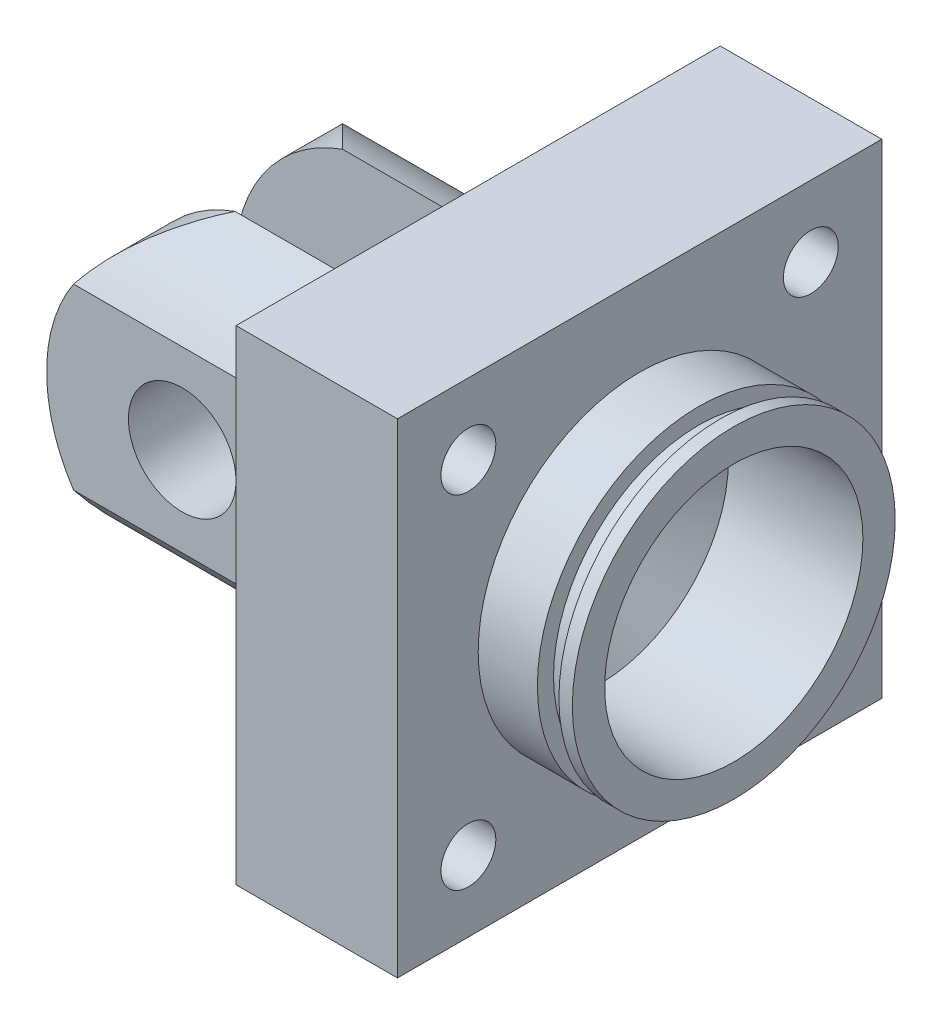
SolidWorks part; units mm, degrees
ref_plane "Front Plane" through (0, 0, 0) normal (0, 0, 1) x (1, 0, 0)
ref_plane "Top Plane" through (0, 0, 0) normal (0, 1, 0) x (1, 0, 0)
ref_plane "Right Plane" through (0, 0, 0) normal (1, 0, 0) x (0, 0, -1)
sketch "Sketch1" plane through (0, 0, 0) normal (0, 0, 1) x (1, 0, 0)
  line L0 (0, 0) -> (55.2, 0)
  dimension "D1" = 55.2
revolve "Revolve-Thin1" add sketch "Sketch1" angle 360 about L0 wall 30
sketch "Sketch2" plane through (55.2, 0, 0) normal (1, 0, 0) x (0, 0, -1)
  line L1 (-45, 45) -> (45, 45)
  line L2 (-45, 45) -> (-45, -45)
  line L3 (-45, -45) -> (45, -45)
  line L4 (45, 45) -> (45, -45)
  line L5 (-45, 45) -> (45, -45) construction
  line L6 (-45, -45) -> (45, 45) construction
  point P0 (0, 0)
  dimension "D1" = 90
  dimension "D2" = 90
extrude "Boss-Extrude1" add sketch "Sketch2" along normal blind 30
sketch "Sketch8" plane through (0, 0, 0) normal (0, 0, 1) x (1, 0, 0)
  line L0 (0, 0) -> (96.2, 0)
  dimension "D1" = 96.2
revolve "Revolve-Thin2" add sketch "Sketch8" angle 360 about L0 wall 30
sketch "Sketch11" plane through (0, 0, 0) normal (0, 1, 0) x (1, 0, 0)
  line L0 (0, 0) -> (100.2, 0)
  dimension "D1" = 100.2
revolve "Revolve-Thin3" add sketch "Sketch11" angle 360 about L0 wall 27
sketch "Sketch14" plane through (100.2, 0, 0) normal (1, 0, 0) x (0, 0, -1)
  point P0 (0, 0)
sketch "Sketch15" plane through (0, 0, 0) normal (0, 0, 1) x (1, 0, 0)
  line L0 (100.2, 0) -> (102.7, 0)
  dimension "D1" = 2.5
revolve "Revolve-Thin4" add sketch "Sketch15" angle 360 about L0 wall 30
sketch "Sketch16" plane through (0, 0, 0) normal (-1, 0, 0) x (0, 0, 1)
  line L1 (-10, -35.8221) -> (10, -35.8221)
  line L2 (-10, -35.8221) -> (-10, 35.8221)
  line L3 (-10, 35.8221) -> (10, 35.8221)
  line L4 (10, -35.8221) -> (10, 35.8221)
  line L5 (-10, -35.8221) -> (10, 35.8221) construction
  line L6 (-10, 35.8221) -> (10, -35.8221) construction
  point P0 (0, 0)
  dimension "D1" = 20
extrude "Cut-Extrude1" cut sketch "Sketch16" against normal blind 55.2
sketch "Sketch17" plane through (0, 0, 0) normal (-1, 0, 0) x (0, 0, 1)
  line L1 (-25, -36.9353) -> (25, -36.9353)
  line L2 (-25, -36.9353) -> (-25, 36.9353)
  line L3 (-25, 36.9353) -> (25, 36.9353)
  line L4 (25, -36.9353) -> (25, 36.9353)
  line L5 (-25, -36.9353) -> (25, 36.9353) construction
  line L6 (-25, 36.9353) -> (25, -36.9353) construction
  point P0 (0, 0)
  dimension "D1" = 50
extrude "Cut-Extrude2" cut sketch "Sketch17" against normal blind 55.2 flip side to cut
sketch "Sketch19" plane through (0, 0, 25) normal (0, 0, 1) x (1, 0, 0)
  circle A0 centre (25.2, 0) radius 10
  dimension "D2" = 20
  dimension "D1" = 25.2
extrude "Cut-Extrude3" cut sketch "Sketch19" against normal through all
sketch "Sketch22" plane through (0, 0, -25) normal (0, 0, -1) x (-1, 0, 0)
  line L1 (-23.6499, 34.3605) -> (9.9849, 34.3605)
  line L2 (-23.6499, 34.3605) -> (-23.6499, -35.6681)
  line L3 (-23.6499, -35.6681) -> (9.9849, -35.6681)
  line L4 (9.9849, 34.3605) -> (9.9849, -35.6681)
  line L5 (-23.6499, 34.3605) -> (9.9849, -35.6681) construction
  line L6 (-23.6499, -35.6681) -> (9.9849, 34.3605) construction
  circle A0 centre (-30, 0) radius 30
  point P3 (-6.8325, -0.6538)
  line M7 (0, -16.5831) -> (0, 16.5831)
  line M8 (0, 16.5831) -> (-55.2, 16.5831)
  line M10 (-55.2, -16.5831) -> (0, -16.5831)
  dimension "D1" = 60
extrude "Cut-Extrude4" cut sketch "Sketch22" against normal through all contours A0 M7 M8 | A0 L2 L3 L4 L1 M8 M7 M10 | A0 M10 M7 region at (6.8325, 33.5836, -25) region at (1.4758, 12.5096, -25) region at (1.4758, -12.5096, -25)
hole_wizard "Tap Drill for M1.2x0.25 Tap2" positions "Sketch25" profile "Sketch26" hole size "M1.2x0.25" standard "ISO"
sketch "Sketch25" plane through (102.7, 0, 0) normal (1, 0, 0) x (0, 0, -1)
  point P0 (0, 0)
sketch "Sketch26" plane through (102.7, 0, 0) normal (0, 1, 0) x (0, 0, -1)
  line L0 (0, 0) -> (0, 39.4207)
  line L1 (0, 39.4207) -> (24, 25)
  line L2 (24, 25) -> (24, 0)
  line L5 (24, 0) -> (0, 0)
  line L10 (0, 39.4207) -> (-24, 25) construction
  line L11 (0, -6.35) -> (0, 107.95) construction
  dimension "Hole Dia." = 48
  dimension "Hole Depth" = 25
  dimension "Drill Angle" = 118
sketch "Sketch30" plane through (85.2, 0, 0) normal (1, 0, 0) x (0, 0, -1)
  line L0 (-45, -45) -> (-31.8198, -31.8198)
  circle A0 centre (0, 0) radius 45
hole_wizard "M12 Tapped Hole2" positions "Sketch31" profile "Sketch32" tap size "M12" standard "ISO"
sketch "Sketch31" plane through (85.2, 0, 0) normal (1, 0, 0) x (0, 0, -1)
  point P0 (-31.8198, -31.8198)
sketch "Sketch32" plane through (85.2, -31.8198, 31.8198) normal (0, 1, 0) x (0, 0, -1)
  line L0 (0, 0) -> (0, 23.0644)
  line L1 (0, 23.0644) -> (5.1, 20)
  line L2 (5.1, 20) -> (5.1, 0)
  line L5 (5.1, 0) -> (0, 0)
  line L10 (0, 23.0644) -> (-5.1, 20) construction
  line L11 (0, -6.35) -> (0, 107.95) construction
  dimension "Tap Drill Dia." = 10.2
  dimension "Tap Drill Depth" = 20
  dimension "Drill Angle" = 118
cosmetic thread "Hole Thread5" parameters "D1"=15, "D2"=11.2
pattern_circular "CirPattern1" count 4 every 90 about axis through (77.7, 0, 0) along (-1, 0, 0) of "M12 Tapped Hole2" reverse direction yes
cosmetic thread "Hole Thread6" parameters "D1"=15, "D2"=11.2
cosmetic thread "Hole Thread7" parameters "D1"=15, "D2"=11.2
cosmetic thread "Hole Thread8" parameters "D1"=15, "D2"=11.2
sketch "Sketch43" plane through (0, -45, 0) normal (0, -1, 0) x (-1, 0, 0)
  point P0 (-70.2, 0)
hole_wizard "M16x1.5 Tapped Hole3" positions "3DSketch7" profile "Sketch44" tap size "M16x1.5" standard "ISO"
sketch3d "3DSketch7"
  point P0 (70.2, -45, 0)
sketch "Sketch44" plane through (70.2, -45, 0) normal (1, 0, 0) x (0, 0, -1)
  line L0 (0, 0) -> (0, 20.3562)
  line L1 (0, 20.3562) -> (7.25, 16)
  line L2 (7.25, 16) -> (7.25, 0)
  line L5 (7.25, 0) -> (0, 0)
  line L10 (0, 20.3562) -> (-7.25, 16) construction
  line L11 (0, -6.35) -> (0, 107.95) construction
  dimension "Tap Drill Dia." = 14.5
  dimension "Tap Drill Depth" = 16
  dimension "Drill Angle" = 118
cosmetic thread "Hole Thread4" parameters "D1"=11, "D2"=16
sketch "Sketch45" plane through (0, -45, 0) normal (0, -1, 0) x (1, 0, 0)
  circle A0 centre (70.2, 0) radius 1.7
  dimension "D1" = 3.4
extrude "Cut-Extrude5" cut sketch "Sketch45" against normal up to next
ref_axis "Axis1" through (149.0573, 0, 0) along (-1, 0, 0)
ref_plane "Plane2" through (85.2, 0, 0) normal (1, 0, 0) x (0, 0, -1)
